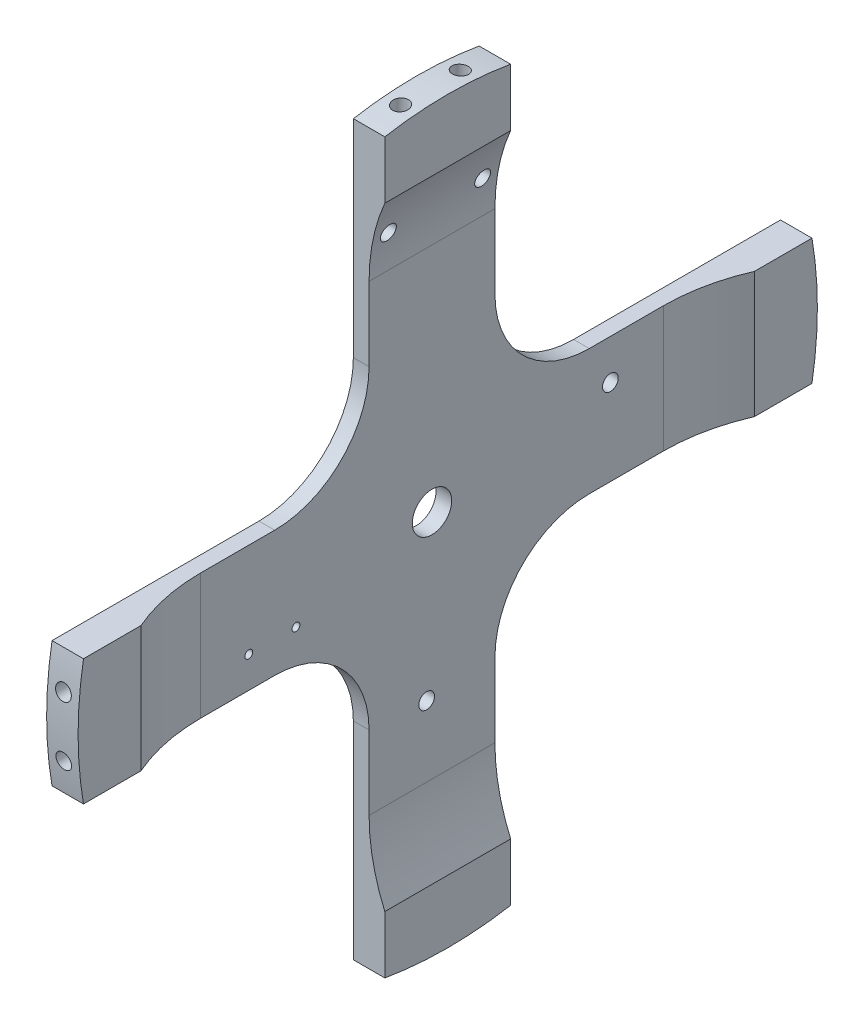
SolidWorks part; units mm, degrees
ref_plane "Front Plane" through (0, 0, 0) normal (0, 0, 1) x (1, 0, 0)
ref_plane "Top Plane" through (0, 0, 0) normal (0, 1, 0) x (1, 0, 0)
ref_plane "Right Plane" through (0, 0, 0) normal (1, 0, 0) x (0, 0, -1)
sketch "Sketch1" plane through (0, 0, 0) normal (1, 0, 0) x (0, 0, -1)
  line L0 (0, 0) -> (0, -152.4)
  line L1 (-3.808, 0) -> (25.4, 0)
  line L2 (25.4, 0) -> (25.4, -147.0474)
  line L3 (0, 0) -> (-25.4, 0)
  line L4 (-25.4, 0) -> (-25.4, -147.0474)
  line L5 (0, -25.4) -> (-147.0474, -25.4)
  line L6 (0, 3.808) -> (0, -25.4)
  line L7 (0, 0) -> (0, 25.4)
  line L8 (0, 25.4) -> (-147.0474, 25.4)
  line L9 (-25.4, 0) -> (-25.4, 147.0474)
  line L10 (3.808, 0) -> (-25.4, 0)
  line L11 (0, 0) -> (25.4, 0)
  line L12 (25.4, 0) -> (25.4, 147.0474)
  line L13 (0, 25.4) -> (147.0474, 25.4)
  line L14 (0, -3.808) -> (0, 25.4)
  line L15 (0, 0) -> (0, -25.4)
  line L16 (0, -25.4) -> (147.0474, -25.4)
  circle A0 centre (0, 0) radius 152.4
  circle A1 centre (0, 0) radius 149.225
  circle A2 centre (0, 0) radius 7.9502
  point P29 (0, 0)
  dimension "D1" = 3.175
  dimension "D2" = 4
  dimension "D3" = 152.4
extrude "Boss-Extrude1" add sketch "Sketch1" along normal blind 6.35 contours L12 A1 L9 L8 L13 | L16 A1 L13 L12 L2 | L8 A1 L5 L4 L9 | L4 A1 L0 L5 | L0 A1 L2 L16 | A2 L15 L16 L2 L11 | A2 L10 L4 L5 L15 | A2 L14 L8 L9 L10 | A2 L11 L12 L13 L14 region at (0, -13.4774, -13.4774) region at (0, -13.4774, 13.4774) region at (0, 13.4774, 13.4774) region at (0, 13.4774, -13.4774) region at (0, -86.9523, -12.6626) region at (0, -86.9523, 12.6626) region at (0, 0, 86.9523) region at (0, 0, -86.9523) region at (0, 86.9523, 0)
sketch "Sketch2" plane through (0, 0, 0) normal (-1, 0, 0) x (0, 0, 1)
  line L0 (-147.0474, 25.4) -> (-147.0474, -25.4)
  line L1 (-149.225, 0) -> (-123.825, 0)
  line L2 (-123.825, 0) -> (-123.825, 25.4)
  line L3 (-123.825, 25.4) -> (-123.5213, 25.2877)
  line L4 (-123.825, 0) -> (-123.825, -25.4)
  line L5 (0, 123.825) -> (-25.4, 123.825)
  line L6 (0, 123.825) -> (25.4, 123.825)
  line L7 (123.825, 0) -> (123.825, 25.4)
  line L8 (25.4, -147.0474) -> (25.4, -25.4)
  line L9 (25.4, -25.4) -> (147.0474, -25.4)
  line L10 (147.0474, 25.4) -> (25.4, 25.4)
  line L11 (25.4, 25.4) -> (25.4, 147.0474)
  line L12 (-25.4, 147.0474) -> (-25.4, 25.4)
  line L13 (-25.4, 25.4) -> (-147.0474, 25.4)
  line L14 (-147.0474, -25.4) -> (-25.4, -25.4)
  line L15 (-25.4, -25.4) -> (-25.4, -147.0474)
  line L16 (25.4, -147.0474) -> (25.4, -25.4)
  line L17 (25.4, -25.4) -> (147.0474, -25.4)
  line L18 (147.0474, 25.4) -> (25.4, 25.4)
  line L19 (25.4, 25.4) -> (25.4, 147.0474)
  line L20 (-25.4, 147.0474) -> (-25.4, 25.4)
  line L22 (-147.0474, -25.4) -> (-25.4, -25.4)
  line L23 (-25.4, -25.4) -> (-25.4, -147.0474)
  line L24 (123.825, 0) -> (123.825, -25.4)
  line L25 (0, -123.825) -> (25.4, -123.825)
  line L26 (0, -123.825) -> (-25.4, -123.825)
  line L35 (-25.4, 25.4) -> (-147.0474, 25.4)
  arc A4 (147.0474, -25.4) -> (147.0474, 25.4) centre (0, 0) ccw
  arc A5 (25.4, 147.0474) -> (-25.4, 147.0474) centre (0, 0) ccw
  arc A6 (-147.0474, 25.4) -> (-147.0474, -25.4) centre (0, 0) ccw
  arc A7 (-25.4, -147.0474) -> (25.4, -147.0474) centre (0, 0) ccw
  arc A8 (147.0474, -25.4) -> (147.0474, 25.4) centre (0, 0) ccw
  arc A9 (25.4, 147.0474) -> (-25.4, 147.0474) centre (0, 0) ccw
  arc A10 (-147.0474, 25.4) -> (-147.0474, -25.4) centre (0, 0) ccw
  arc A11 (-25.4, -147.0474) -> (25.4, -147.0474) centre (0, 0) ccw
  point P34 (-25.4, 0)
  point P35 (0, 0)
  line M16 (25.4, -147.0474) -> (25.4, -25.4)
  arc M18 (147.0474, -25.4) -> (147.0474, 25.4) centre (0, 0) ccw
  line M19 (147.0474, 25.4) -> (25.4, 25.4)
  line M20 (25.4, 25.4) -> (25.4, 147.0474)
  arc M21 (25.4, 147.0474) -> (-25.4, 147.0474) centre (0, 0) ccw
  line M22 (-25.4, 147.0474) -> (-25.4, 25.4)
  line M23 (-25.4, 25.4) -> (-147.0474, 25.4)
  arc M24 (-147.0474, 25.4) -> (-147.0474, -25.4) centre (0, 0) ccw
  line M25 (-147.0474, -25.4) -> (-25.4, -25.4)
  arc M27 (-25.4, -147.0474) -> (25.4, -147.0474) centre (0, 0) ccw
  dimension "D2" = 4
  dimension "D1" = 0
extrude "Boss-Extrude2" add sketch "Sketch2" against normal blind 12.7 contours L5 L6 M20 M21 M22 | L7 L24 L17 M18 M19 | L25 L26 L23 M27 M16 | L4 L1 L0 M25 | L1 L0 M24 | L1 L2 L0 M23 | L1 L0 M24 region at (0, 12.7, -135.4362) region at (0, 9.5343, -147.919) region at (0, -12.7, -135.4362) region at (0, -9.5343, -147.919) region at (0, 136.1717, 0) region at (0, -136.1717, 0) region at (0, 0, 136.1717)
fillet "Fillet1" radius 38.1 4 edges at (3.175, -25.4, -25.4) (3.175, 25.4, -25.4) (3.175, 25.4, 25.4) (3.175, -25.4, 25.4)
fillet "Fillet2" radius 76.2 4 edges at (6.35, 0, 123.825) (6.35, -123.825, 0) (6.35, 0, -123.825) (6.35, 123.825, 0)
ref_plane "Plane2" through (0, 0, -149.225) normal (0, 0, -1) x (-1, 0, 0)
sketch "Sketch3" plane through (0, 0, -149.225) normal (0, 0, -1) x (-1, 0, 0)
  line L4 (0, -25.4) -> (0, 25.4)
  line L5 (0, 25.4) -> (-12.7, 25.4)
  line L6 (-12.7, 25.4) -> (-12.7, -25.4)
  line L7 (-12.7, -25.4) -> (0, -25.4)
  line L8 (0, -25.4) -> (0, 25.4)
  line L10 (-12.7, 25.4) -> (-12.7, -25.4)
  line L11 (-12.7, -25.4) -> (0, -25.4)
  line L13 (0, 25.4) -> (-12.7, 25.4)
  circle A0 centre (-6.35, 12.7) radius 3.175
  circle A1 centre (-6.35, -11.43) radius 3.175
  dimension "D3" = 13.97
  dimension "D4" = 6.35
  dimension "D5" = 6.35
  dimension "D1" = 0
extrude "Cut-Extrude1" cut sketch "Sketch3" against normal blind 12.7 contours A0 | A1 region at (6.35, 12.7, -149.225) region at (6.35, -11.43, -149.225)
pattern_circular "CirPattern1" count 4 over 360 about axis through (0, 0, 0) along (1, 0, 0) of "Cut-Extrude1"
sketch "Sketch4" plane through (0, 0, 0) normal (-1, 0, 0) x (0, 0, 1)
  line L8 (-147.0474, -25.4) -> (-63.5, -25.4)
  line L9 (-25.4, -63.5) -> (-25.4, -147.0474)
  line L10 (25.4, -147.0474) -> (25.4, -63.5)
  line L11 (63.5, -25.4) -> (147.0474, -25.4)
  line L12 (147.0474, 25.4) -> (63.5, 25.4)
  line L13 (25.4, 63.5) -> (25.4, 147.0474)
  line L14 (-25.4, 147.0474) -> (-25.4, 63.5)
  line L15 (-63.5, 25.4) -> (-147.0474, 25.4)
  line L16 (-147.0474, -25.4) -> (-63.5, -25.4)
  line L17 (-25.4, -63.5) -> (-25.4, -147.0474)
  line L18 (25.4, -147.0474) -> (25.4, -63.5)
  line L19 (63.5, -25.4) -> (147.0474, -25.4)
  line L20 (147.0474, 25.4) -> (63.5, 25.4)
  line L21 (25.4, 63.5) -> (25.4, 147.0474)
  line L22 (-25.4, 147.0474) -> (-25.4, 63.5)
  line L25 (-63.5, 25.4) -> (-147.0474, 25.4)
  circle A2 centre (73.9775, -12.7635) radius 1.5875
  circle A3 centre (54.9275, -12.7635) radius 1.5875
  circle A4 centre (19.05, 107.95) radius 3.175
  circle A5 centre (-19.05, 107.95) radius 3.175
  arc A8 (-147.0474, 25.4) -> (-147.0474, -25.4) centre (0, 0) ccw
  arc A9 (-25.4, -63.5) -> (-63.5, -25.4) centre (-63.5, -63.5) ccw
  arc A10 (-25.4, -147.0474) -> (25.4, -147.0474) centre (0, 0) ccw
  arc A11 (63.5, -25.4) -> (25.4, -63.5) centre (63.5, -63.5) ccw
  arc A12 (147.0474, -25.4) -> (147.0474, 25.4) centre (0, 0) ccw
  arc A13 (25.4, 63.5) -> (63.5, 25.4) centre (63.5, 63.5) ccw
  arc A14 (25.4, 147.0474) -> (-25.4, 147.0474) centre (0, 0) ccw
  arc A16 (-147.0474, 25.4) -> (-147.0474, -25.4) centre (0, 0) ccw
  arc A17 (-25.4, -63.5) -> (-63.5, -25.4) centre (-63.5, -63.5) ccw
  arc A18 (-25.4, -147.0474) -> (25.4, -147.0474) centre (0, 0) ccw
  arc A19 (63.5, -25.4) -> (25.4, -63.5) centre (63.5, -63.5) ccw
  arc A20 (147.0474, -25.4) -> (147.0474, 25.4) centre (0, 0) ccw
  arc A21 (25.4, 63.5) -> (63.5, 25.4) centre (63.5, 63.5) ccw
  arc A22 (25.4, 147.0474) -> (-25.4, 147.0474) centre (0, 0) ccw
  arc A27 (-63.5, 25.4) -> (-25.4, 63.5) centre (-63.5, 63.5) ccw
  arc A28 (-63.5, 25.4) -> (-25.4, 63.5) centre (-63.5, 63.5) ccw
  dimension "D1" = 0
extrude "Cut-Extrude2" cut sketch "Sketch4" against normal through all contours A2 | A3 | A4 | A5 region at (0, -12.7635, 73.9775) region at (0, -12.7635, 54.9275) region at (0, 107.95, 19.05) region at (0, 107.95, -19.05)
sketch "Sketch5" plane through (0, 0, 0) normal (-1, 0, 0) x (0, 0, 1)
  line L8 (-147.0474, -25.4) -> (-63.5, -25.4)
  line L9 (-25.4, -63.5) -> (-25.4, -147.0474)
  line L10 (25.4, -147.0474) -> (25.4, -63.5)
  line L11 (63.5, -25.4) -> (147.0474, -25.4)
  line L12 (147.0474, 25.4) -> (63.5, 25.4)
  line L13 (25.4, 63.5) -> (25.4, 147.0474)
  line L14 (-25.4, 147.0474) -> (-25.4, 63.5)
  line L15 (-63.5, 25.4) -> (-147.0474, 25.4)
  line L16 (-147.0474, -25.4) -> (-63.5, -25.4)
  line L17 (-25.4, -63.5) -> (-25.4, -147.0474)
  line L18 (25.4, -147.0474) -> (25.4, -63.5)
  line L19 (63.5, -25.4) -> (147.0474, -25.4)
  line L20 (147.0474, 25.4) -> (63.5, 25.4)
  line L21 (25.4, 63.5) -> (25.4, 147.0474)
  line L22 (-25.4, 147.0474) -> (-25.4, 63.5)
  line L25 (-63.5, 25.4) -> (-147.0474, 25.4)
  circle A0 centre (-72.0135, 9.2761) radius 3.175
  circle A1 centre (2.1634, -64.9008) radius 3.175
  arc A8 (-147.0474, 25.4) -> (-147.0474, -25.4) centre (0, 0) ccw
  arc A9 (-25.4, -63.5) -> (-63.5, -25.4) centre (-63.5, -63.5) ccw
  arc A10 (-25.4, -147.0474) -> (25.4, -147.0474) centre (0, 0) ccw
  arc A11 (63.5, -25.4) -> (25.4, -63.5) centre (63.5, -63.5) ccw
  arc A12 (147.0474, -25.4) -> (147.0474, 25.4) centre (0, 0) ccw
  arc A13 (25.4, 63.5) -> (63.5, 25.4) centre (63.5, 63.5) ccw
  arc A14 (25.4, 147.0474) -> (-25.4, 147.0474) centre (0, 0) ccw
  arc A16 (-147.0474, 25.4) -> (-147.0474, -25.4) centre (0, 0) ccw
  arc A17 (-25.4, -63.5) -> (-63.5, -25.4) centre (-63.5, -63.5) ccw
  arc A18 (-25.4, -147.0474) -> (25.4, -147.0474) centre (0, 0) ccw
  arc A19 (63.5, -25.4) -> (25.4, -63.5) centre (63.5, -63.5) ccw
  arc A20 (147.0474, -25.4) -> (147.0474, 25.4) centre (0, 0) ccw
  arc A21 (25.4, 63.5) -> (63.5, 25.4) centre (63.5, 63.5) ccw
  arc A22 (25.4, 147.0474) -> (-25.4, 147.0474) centre (0, 0) ccw
  arc A25 (-63.5, 25.4) -> (-25.4, 63.5) centre (-63.5, 63.5) ccw
  arc A26 (-63.5, 25.4) -> (-25.4, 63.5) centre (-63.5, 63.5) ccw
  dimension "D1" = 0
extrude "Cut-Extrude3" cut sketch "Sketch5" against normal through all contours A1 | A0 region at (0, 9.2761, -72.0135) region at (0, -64.9008, 2.1634)
